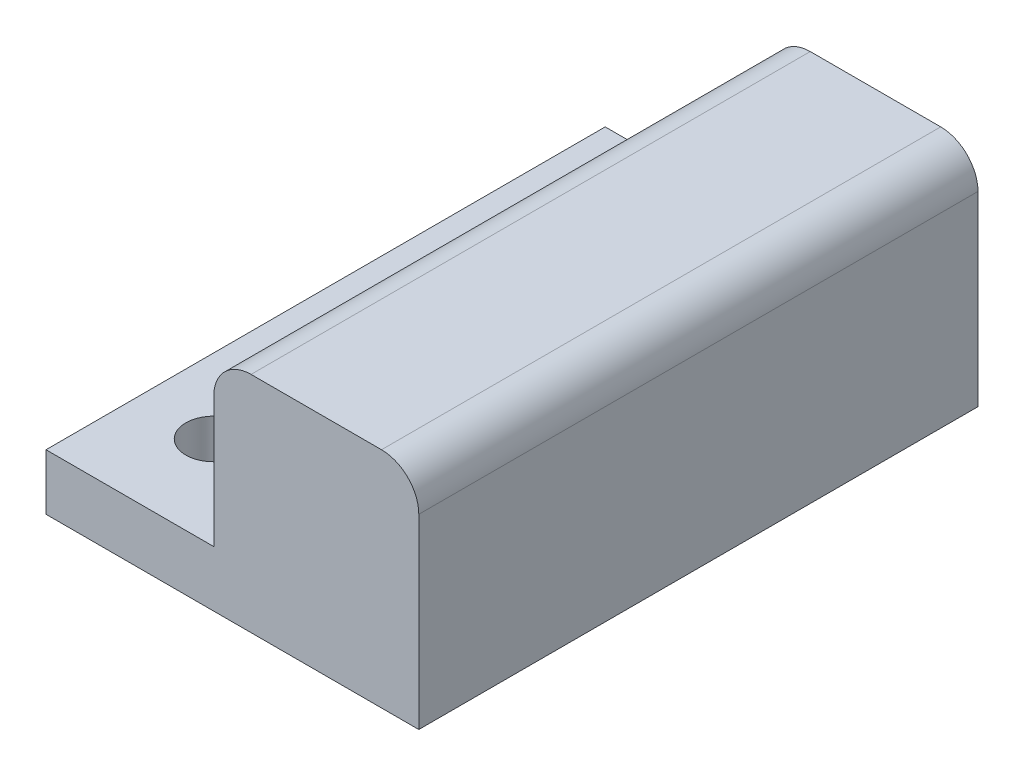
SolidWorks part; units mm, degrees
ref_plane "Front Plane" through (0, 0, 0) normal (0, 0, 1) x (1, 0, 0)
ref_plane "Top Plane" through (0, 0, 0) normal (0, 1, 0) x (1, 0, 0)
ref_plane "Right Plane" through (0, 0, 0) normal (1, 0, 0) x (0, 0, -1)
sketch "Sketch1" plane through (0, 0, 0) normal (0, 1, 0) x (1, 0, 0)
  line L0 (0, 0) -> (0, -25.4) construction
  line L1 (-20.32, 6.35) -> (5.08, 6.35)
  line L2 (-20.32, 6.35) -> (-20.32, -31.75)
  line L3 (-20.32, -31.75) -> (5.08, -31.75)
  line L4 (5.08, 6.35) -> (5.08, -31.75)
  circle A0 centre (0, 0) radius 1.905
  circle A1 centre (0, -25.4) radius 1.905
  point P6 (-20.32, -12.7)
  point P12 (0, -12.7)
  dimension "D1" = 25.4
  dimension "D2" = 3.81
  dimension "D3" = 3.81
  dimension "D4" = 5.08
  dimension "D5" = 38.1
  dimension "D6" = 25.4
extrude "Boss-Extrude1" add sketch "Sketch1" along normal blind 3.81
sketch "Sketch2" plane through (0, 3.81, 0) normal (0, 1, 0) x (1, 0, 0)
  line L0 (-20.32, 6.35) -> (-20.32, -31.75)
  line L1 (-20.32, -31.75) -> (-6.35, -31.75)
  line L2 (-20.32, -31.75) -> (5.08, -31.75) construction
  line L3 (-6.35, -31.75) -> (-6.35, 6.35)
  line L4 (5.08, 6.35) -> (-20.32, 6.35) construction
  line L5 (-6.35, 6.35) -> (-8.89, 6.35)
  line L6 (-8.89, 6.35) -> (-8.89, -29.21)
  line L7 (-8.89, -29.21) -> (-17.78, -29.21)
  line L8 (-17.78, -29.21) -> (-17.78, 6.35)
  line L9 (-17.78, 6.35) -> (-20.32, 6.35)
  dimension "D1" = 2.54
  dimension "D2" = 8.89
  dimension "D3" = 2.54
extrude "Boss-Extrude2" add sketch "Sketch2" along normal blind 8.89 contours L0 L1 L3 L5 L6 L7 L8 L9
sketch "Sketch3" plane through (0, 12.7, 0) normal (0, 1, 0) x (1, 0, 0)
  line L1 (-20.32, 6.35) -> (-6.35, 6.35)
  line L2 (-20.32, 6.35) -> (-20.32, -31.75)
  line L3 (-20.32, -31.75) -> (-6.35, -31.75)
  line L4 (-6.35, 6.35) -> (-6.35, -31.75)
extrude "Boss-Extrude3" add sketch "Sketch3" along normal blind 2.54
chamfer "Chamfer1" distance 1.27 angle 45 2 edges at (-8.89, 12.7, 11.43) (-17.78, 12.7, 11.43)
mirror "Mirror1" about plane through (5.08, 3.81, -6.35) normal (-1, 0, 0) of bodies 103
delete or keep bodies "Body-Delete/Keep 1" type delete bodies bodies 103
fillet "Fillet1" radius 2.54 2 edges at (30.48, 15.24, 12.7) (16.51, 15.24, 12.7)
